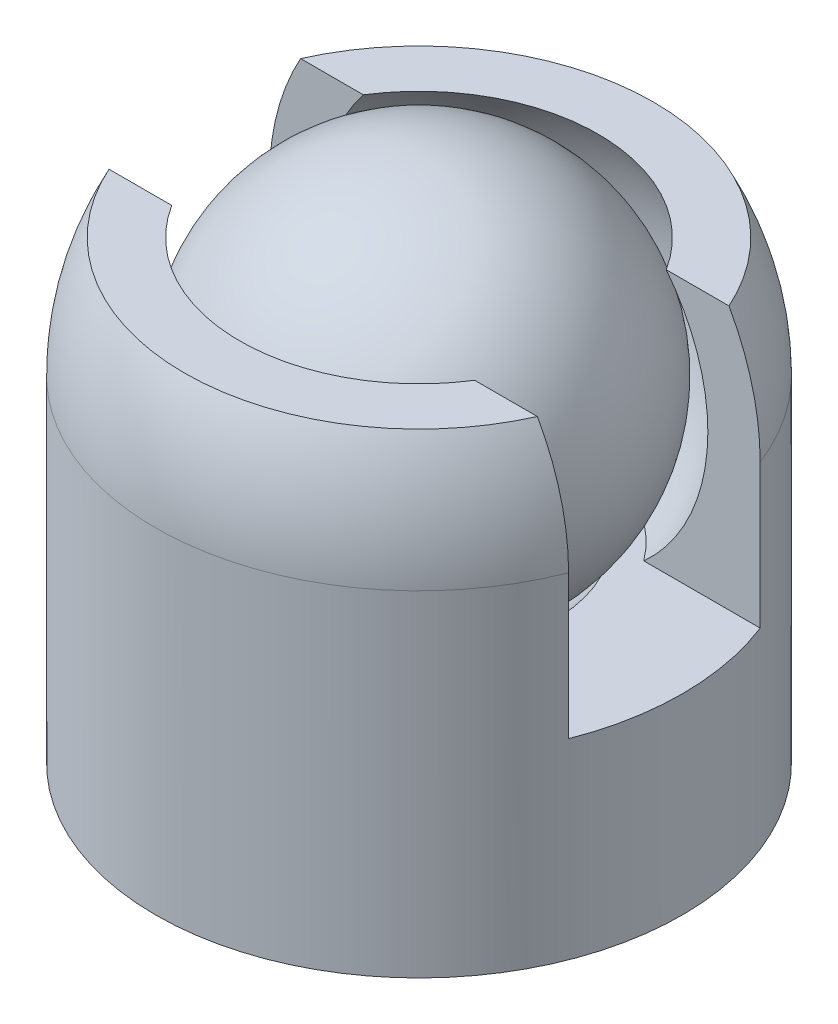
SolidWorks part; units mm, degrees
ref_plane "Front Plane" through (0, 0, 0) normal (0, 0, 1) x (1, 0, 0)
ref_plane "Top Plane" through (0, 0, 0) normal (0, 1, 0) x (1, 0, 0)
ref_plane "Right Plane" through (0, 0, 0) normal (1, 0, 0) x (0, 0, -1)
sketch "Sketch1" plane through (0, 0, 0) normal (0, 1, 0) x (1, 0, 0)
  line L0 (0, 5.5) -> (0, -5.5) construction
  line L2 (-6.5, 0) -> (7.0815, 0) construction
  circle A1 centre (-6.5, 0) radius 1
  arc A3 (-4.4371, -3.25) -> (4.4371, -3.25) centre (0, 0) ccw
  arc A4 (-6.5, 2) -> (-6.5, -2) centre (-6.5, 0) ccw
  arc A5 (-6.5, 2) -> (-4.4371, 3.25) centre (-6.9726, 5.1072) ccw
  arc A6 (-6.5, -2) -> (-4.4371, -3.25) centre (-6.9726, -5.1072) cw
  arc A7 (6.5, -2) -> (4.4371, -3.25) centre (6.9726, -5.1072) ccw
  arc A8 (6.5, 2) -> (4.4371, 3.25) centre (6.9726, 5.1072) cw
  arc A9 (6.5, 2) -> (6.5, -2) centre (6.5, 0) cw
  circle A10 centre (6.5, 0) radius 1
  arc A11 (4.4371, 3.25) -> (-4.4371, 3.25) centre (0, 0) ccw
  dimension "D1" = 11
  dimension "D2" = 2
  dimension "D4" = 6.5
  dimension "D3" = 2
extrude "Boss-Extrude1" add sketch "Sketch1" along normal blind 4 contours A11 A10 A1 region at (0, 0, 0)
sketch "Sketch10" plane through (0, 0, 0) normal (0, 0, 1) x (1, 0, 0)
  line L0 (0, 3) -> (0, 12)
  line L1 (4.4371, 4) -> (-4.4371, 4) construction
  arc A0 (0, 12) -> (0, 3) centre (0, 7.5) cw
  dimension "D1" = 9
  dimension "D2" = 1
revolve "Cut-Revolve2" cut sketch "Sketch10" angle 360 about L0
sketch "Sketch22" plane through (0, 4, 0) normal (0, 1, 0) x (1, 0, 0)
  circle A0 centre (0, 0) radius 2
  dimension "D1" = 4
extrude "Cut-Extrude4" cut sketch "Sketch22" against normal blind 2.5
sketch "Sketch23" plane through (0, 1.5, 0) normal (0, 1, 0) x (1, 0, 0)
  circle A0 centre (0, 0) radius 1.25
  dimension "D1" = 2.5
extrude "Cut-Extrude5" cut sketch "Sketch23" against normal through all
fillet "Fillet1" radius 0.75 1 edges at (0, 1.5, 2)
sketch "Sketch13" plane through (0, 4, 0) normal (0, 1, 0) x (1, 0, 0)
  circle A0 centre (0, 0) radius 5.5
  arc A1 (4.4371, 3.25) -> (-4.4371, 3.25) centre (0, 0) ccw construction
sketch "Sketch16" plane through (0, 4, 0) normal (0, 1, 0) x (1, 0, 0)
  circle A0 centre (0, 0) radius 3.5
  dimension "D1" = 7
sketch "Sketch18" plane through (0, 0, 0) normal (1, 0, 0) x (0, 0, -1)
  line L0 (0, 11) -> (0, 3)
  line L2 (3.5, 4) -> (-3.5, 4) construction
  arc A0 (0, 3) -> (0, 11) centre (0, 7) ccw
  dimension "D1" = 8
  dimension "D2" = 1
sketch "Sketch19" plane through (0, 0, 0) normal (1, 0, 0) x (0, 0, -1)
  line L1 (5.5, 4) -> (-5.5, 4) construction
  line L2 (5.5, 7) -> (5.5, 4)
  line L4 (5.5, 4) -> (3.3541, 4)
  line L5 (3.7417, 9.5) -> (4.899, 9.5)
  arc A0 (0, 3) -> (0, 11) centre (0, 7) ccw construction
  arc A1 (5.5, 7) -> (4.899, 9.5) centre (0, 7) ccw
  arc A3 (3.3541, 4) -> (3.7417, 9.5) centre (0, 7) ccw
  point P23 (0, 7)
  dimension "D2" = 3
  dimension "D3" = 5.5
  dimension "D4" = 2.1459
revolve "Revolve6" add sketch "Sketch19" angle 360 about L0
sketch "Sketch20" plane through (0, 0, 0) normal (1, 0, 0) x (0, 0, -1)
  line L0 (-2, 4) -> (-2, 0) construction
  line L1 (-2, 4) -> (2, 4)
  line L2 (-2, 4) -> (-2, 9.5)
  line L3 (-2, 9.5) -> (2, 9.5)
  line L4 (2, 4) -> (2, 9.5)
  line L5 (0, 4) -> (-3.25, 4) construction
  line L6 (4.899, 9.5) -> (-4.899, 9.5) construction
extrude "Cut-Extrude2" cut sketch "Sketch20" against normal through all both and the other way through all
revolve "Revolve7" add sketch "Sketch18" angle 360 about L0
sketch "Sketch21" plane through (0, 0, 0) normal (0, -1, 0) x (1, 0, 0)
  circle A0 centre (0, 0) radius 5.5
  dimension "D1" = 11
extrude "Cut-Extrude3" cut sketch "Sketch21" against normal through all flip side to cut
